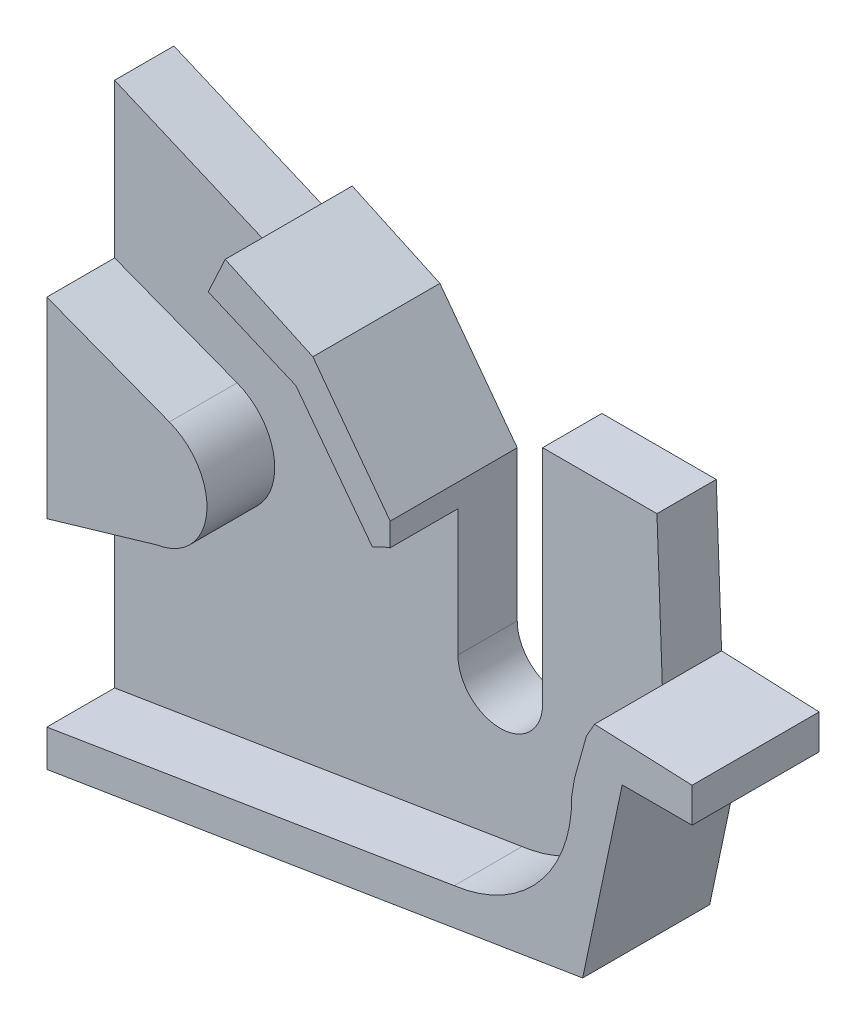
SolidWorks part; units mm, degrees
ref_plane "Front Plane" through (0, 0, 0) normal (0, 0, 1) x (1, 0, 0)
ref_plane "Top Plane" through (0, 0, 0) normal (0, 1, 0) x (1, 0, 0)
ref_plane "Right Plane" through (0, 0, 0) normal (1, 0, 0) x (0, 0, -1)
sketch "Sketch1" plane through (0, 0, 0) normal (0, 0, 1) x (1, 0, 0)
  line L0 (-48.8998, -64.1664) -> (-34.4801, 53.9567) construction
  line L3 (0, 51.4823) -> (78.4652, 51.4823)
  line L4 (78.4652, 0) -> (78.4652, 51.4823)
  line L5 (-0.9054, 14.8469) -> (9.0946, 14.8469)
  line L6 (9.0946, 14.8469) -> (9.0946, -2.1531)
  line L7 (9.0946, -2.1531) -> (-0.9054, -2.1531)
  line L8 (-0.9054, -2.1531) -> (-0.9054, 14.8469)
  line L9 (-12.0436, 28.8286) -> (-0.9054, 14.0572)
  line L10 (-53.3531, 46.4275) -> (-12.0436, 28.8286)
  line L11 (9.0946, 14.8469) -> (9.0946, 29.052)
  line L12 (9.0946, 29.052) -> (22.5946, 29.052)
  line L13 (-62.6952, 31.3187) -> (-26.9826, 17.6419)
  line L14 (-26.9826, 17.6419) -> (-29.4561, 11.1831)
  line L15 (-29.4561, 11.1831) -> (-31.9296, 4.7244)
  line L16 (-71.5207, -8.3096) -> (-28.3713, 4.3526)
  line L17 (-41.4462, 23.181) -> (-41.4462, 0.5157)
  line L18 (-28.3713, 4.3526) -> (-29.4561, 11.1831)
  line L19 (-29.4561, 11.1831) -> (-30.541, 18.0137)
  line L20 (-74.7301, -26.2138) -> (-1.4754, -14.2813)
  line L21 (-1.4754, -14.2813) -> (7.6299, -12.7982)
  line L22 (23.2246, 11.8381) -> (22.2572, 10.123)
  line L23 (23.2246, 11.8381) -> (34.7443, 11.3546)
  line L24 (-0.9054, 14.8469) -> (-0.9054, 20.5391)
  line L25 (-0.9054, 20.5391) -> (-7.2539, 29.052)
  line L26 (-7.2539, 29.052) -> (-10.0368, 32.7838)
  line L27 (-10.0368, 32.7838) -> (-20.3866, 37.57)
  line L28 (-20.3866, 37.57) -> (-22.3905, 33.2367)
  line L29 (-70.8332, -25.579) -> (-70.1459, -29.7983)
  line L30 (-70.1459, -29.7983) -> (21.8227, -14.8175)
  line L31 (21.8227, -14.8175) -> (26.4898, 7.2668)
  line L32 (26.4898, 7.2668) -> (34.7443, 7.2668)
  line L33 (34.7443, 7.2668) -> (34.7443, 11.3546)
  line L34 (-62.6952, 31.3187) -> (-53.3531, 46.4275)
  line L35 (-70.8332, -25.579) -> (-71.5207, -8.3096)
  line L36 (22.5946, 29.052) -> (23.2246, 11.8381)
  line L37 (-41.4462, 0.5157) -> (-41.4462, -25.1234)
  line L38 (-41.4462, 23.181) -> (-41.4462, 41.3549)
  line L39 (22.2572, 10.123) -> (21.4546, 7.2463)
  line L40 (21.4546, 7.2463) -> (20.8501, 5.08)
  line L41 (20.8501, 5.08) -> (20.5233, 3.0772)
  circle A0 centre (4.0946, 2.8469) radius 5
  circle A1 centre (4.0946, 9.8469) radius 5
  circle A2 centre (-29.4561, 11.1831) radius 6.9162
  circle A3 centre (4.5867, 2.8469) radius 15.9383
  point P47 (20.8501, 5.08)
  point P52 (20.5233, 3.0772)
  point P53 (0, 0)
  point P54 (4.0946, 2.8469)
  dimension "D4" = 13.5
  dimension "D1" = 119
  dimension "D2" = 10
  dimension "D3" = 17
extrude "Boss-Extrude2" add sketch "Sketch1" along normal blind 7 contours L0 L37 L20 L21 A3 L9 L10 L13 A2 L16 | L13 L0 L10 L38 | L0 L16 A2 L13 | L16 L0 L13 L17 | L37 L0 L16 | A3 L21 L20 L37 L30 L31 L32 L33 L23 L22 L39 L40 L41 | A3 L11 L6 L7 L8 L9 L21 | A0 L7 L6 | A0 L8 L7 | A3 L41 L40 L39 L22 L36 L12 L11 | A3 L24 L25 L26 L27 L28 L10 L9 | L24 A3 L9 L8 | A2 region at (-40.5994, -22.9578, 0) region at (-41.2933, -0.6473, 0) region at (-23.0236, 5.9076, 0) region at (-40.406, 14.3356, 0) region at (-36.6256, 10.9136, 0) region at (-39.3484, 32.1788, 0) region at (-10.1478, -1.9383, 0) region at (-1.6145, 16.2585, 0) region at (-10.8343, 28.4253, 0) region at (16.9275, 20.4665, 0) region at (0.2115, -1.0363, 0) region at (7.9778, -1.0363, 0)
extrude "Boss-Extrude3" add sketch "Sketch1<7>" along normal blind 15 contours L0 L16 A2 L13 | L19 A2 L15 | L16 L0 L13 L17 | L18 A2 L14 | L15 A2 L18 | L14 A2 L19 | A3 L24 L25 L26 L27 L28 L10 | A3 L21 L20 L37 L30 L31 L32 L33 L23 region at (-40.5994, -22.9578, 0) region at (-40.406, 14.3356, 0) region at (-36.6256, 10.9136, 0) region at (-29.9299, 6.6495, 0) region at (-26.0725, 10.8296, 0) region at (-28.9824, 15.7168, 0) region at (-32.8398, 11.5367, 0) region at (-10.8343, 28.4253, 0)
sketch "Sketch1<7>" plane through (0, 0, 0) normal (0, 0, 1) x (1, 0, 0) same geometry as "Sketch1"
